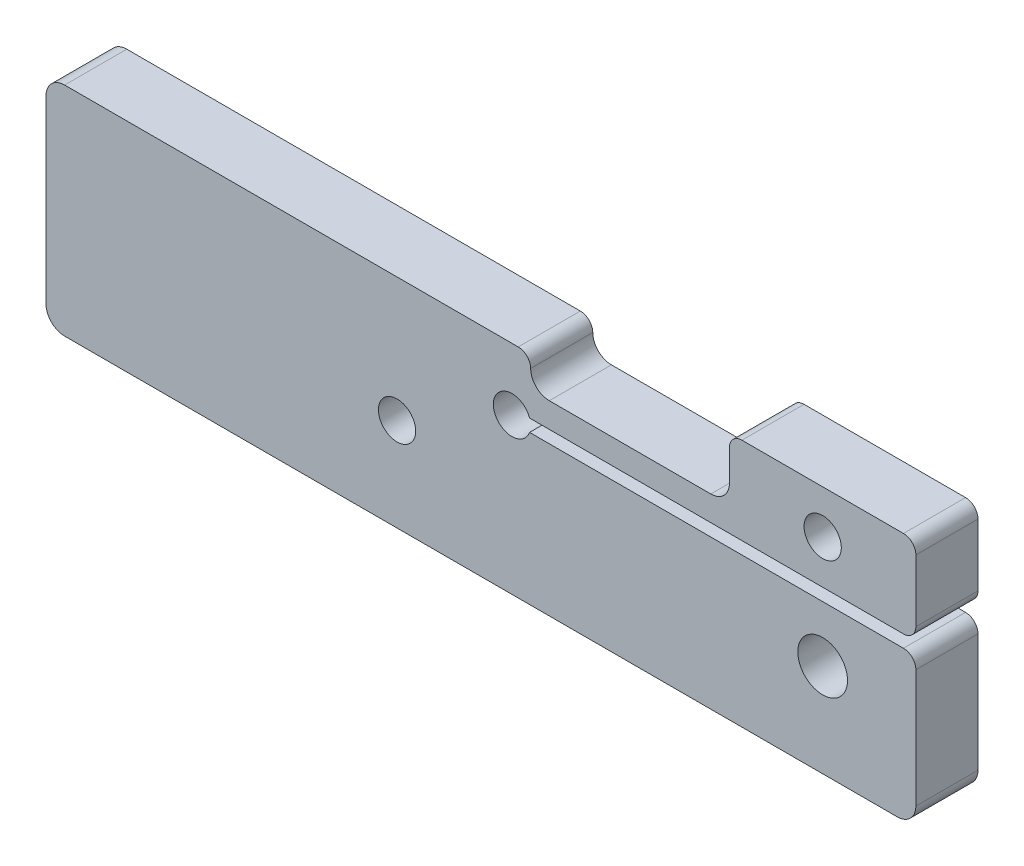
SolidWorks part; units mm, degrees
ref_plane "Front" through (0, 0, 0) normal (0, 0, 1) x (1, 0, 0)
ref_plane "Top" through (0, 0, 0) normal (0, 1, 0) x (1, 0, 0)
ref_plane "Right" through (0, 0, 0) normal (1, 0, 0) x (0, 0, -1)
sketch "Esquisse1" plane through (0, 0, 0) normal (0, 0, 1) x (1, 0, 0)
  line L1 (0, 0) -> (140, 0)
  line L2 (0, 0) -> (0, 35)
  line L3 (0, 35) -> (140, 35)
  line L4 (140, 0) -> (140, 35)
  dimension "D1" = 35
  dimension "D2" = 140
extrude "Boss.-Extru.1" add sketch "Esquisse1" along normal blind 30
sketch "Esquisse2" plane through (0, 0, 30) normal (0, 0, 1) x (1, 0, 0)
  line L0 (0, 0) -> (140, 0) construction
  line L1 (8.5, 0) -> (41.5, 0)
  line L2 (8.5, 0) -> (8.5, 35)
  line L3 (8.5, 35) -> (41.5, 35)
  line L4 (41.5, 0) -> (41.5, 35)
  line L5 (140, 35) -> (0, 35) construction
  line L6 (0, 35) -> (0, 0) construction
  dimension "D1" = 33
  dimension "D2" = 8.5
extrude "Enlèv. mat.-Extru.1" cut sketch "Esquisse2" against normal blind 20
sketch "Esquisse3" plane through (0, 0, 30) normal (0, 0, 1) x (1, 0, 0)
  line L0 (140, 35) -> (41.5, 35) construction
  line L1 (110, 35) -> (140, 35)
  line L2 (110, 35) -> (110, 40)
  line L3 (110, 40) -> (140, 40)
  line L4 (140, 35) -> (140, 40)
  line L5 (140, 0) -> (140, 35) construction
  dimension "D1" = 30
  dimension "D2" = 5
extrude "Boss.-Extru.2" add sketch "Esquisse3" against normal up to vertex (30 mm away)
sketch "Esquisse4" plane through (0, 0, 30) normal (0, 0, 1) x (1, 0, 0)
  line L0 (41.5, 0) -> (140, 0) construction
  line L1 (140, 0) -> (140, 40) construction
  circle A0 centre (75, 25) radius 3
  dimension "D2" = 65
  dimension "D3" = 6
  dimension "D1" = 25
extrude "Enlèv. mat.-Extru.2" cut sketch "Esquisse4" against normal through all both and the other way through all
sketch "Esquisse5" plane through (0, 0, 30) normal (0, 0, 1) x (1, 0, 0)
  line L0 (75, 25) -> (140, 25) construction
  line L1 (140, 0) -> (140, 40) construction
  line L2 (140, 24) -> (140, 26)
  line L3 (140, 26) -> (75, 26)
  line L4 (75, 26) -> (75, 24)
  line L5 (140, 24) -> (75, 24)
  dimension "D1" = 2
extrude "Enlèv. mat.-Extru.3" cut sketch "Esquisse5" against normal through all both and the other way through all
sketch "Esquisse6" plane through (0, 0, 30) normal (0, 0, 1) x (1, 0, 0)
  line L0 (110, 35) -> (41.5, 35) construction
  line L1 (78, 35) -> (110, 35)
  line L2 (78, 35) -> (78, 30)
  line L3 (78, 30) -> (110, 30)
  line L4 (110, 35) -> (110, 30)
  line L5 (140, 26) -> (140, 40) construction
  dimension "D1" = 32
  dimension "D2" = 30
  dimension "D3" = 5
extrude "Enlèv. mat.-Extru.4" cut sketch "Esquisse6" against normal through all both and the other way through all
fillet "Congé1" radius 3 2 edges at (110, 30, 15) (78, 30, 15)
sketch "Esquisse8" plane through (0, 0, 30) normal (0, 0, 1) x (1, 0, 0)
  line L0 (41.5, 0) -> (140, 0) construction
  line L1 (72, 0) -> (140, 0)
  line L3 (106.2756, 24) -> (140, 24)
  line L4 (140, 0) -> (140, 24)
  line L6 (140, 24) -> (77.8284, 24) construction
  line L7 (72, 0) -> (106.2756, 24)
  line L8 (140, 0) -> (140, 24) construction
  line L9 (41.5, 0) -> (140, 0) construction
  dimension "D1" = 35
  dimension "D2" = 68
extrude "Enlèv. mat.-Extru.6" cut sketch "Esquisse8" against normal blind 15
sketch "Esquisse7" plane through (0, 0, 30) normal (0, 0, 1) x (1, 0, 0)
  line L0 (140, 26) -> (140, 40) construction
  line L1 (41.5, 0) -> (72, 0) construction
  circle A0 centre (125, 15) radius 4
  dimension "D1" = 8
  dimension "D2" = 15
  dimension "D3" = 15
extrude "Enlèv. mat.-Extru.5" cut sketch "Esquisse7" against normal through all both and the other way through all
fillet "Congé2" radius 3 4 edges at (140, 0, 7.5) (72, 0, 22.5) (0, 35, 15) (0, 0, 15)
fillet "Congé3" radius 2 12 edges at (106.2756, 24, 22.5) (8.5, 0, 20) (8.5, 35, 20) (41.5, 35, 20) (41.5, 0, 20) (110, 40, 15) (140, 40, 15) (140, 26, 15) (140, 24, 7.5) (78, 34, 0) (78, 35, 15) (78, 34, 30)
sketch "Esquisse10" plane through (0, 0, 30) normal (0, 0, 1) x (1, 0, 0)
  line L0 (140, 33) -> (125, 33) construction
  line L1 (140, 28) -> (140, 38) construction
  line L2 (125, 33) -> (125, 40) construction
  line L3 (138, 40) -> (112, 40) construction
  line L4 (43.5, 0) -> (71.0541, 0) construction
  line L5 (41.5, 2) -> (41.5, 33) construction
  circle A0 centre (56.5, 15) radius 3
  circle A1 centre (125, 33) radius 3
  dimension "D1" = 6
  dimension "D2" = 15
  dimension "D3" = 15
extrude "Enlèv. mat.-Extru.8" cut sketch "Esquisse10" against normal through all both and the other way through all
sketch "Esquisse9" plane through (0, 0, 30) normal (0, 0, 1) x (1, 0, 0)
  line L0 (138, 40) -> (112, 40) construction
  line L1 (0, 0) -> (140, 0)
  line L2 (0, 0) -> (0, 40)
  line L3 (0, 40) -> (140, 40)
  line L4 (140, 0) -> (140, 40)
  line L5 (140, 3) -> (140, 22) construction
extrude "Enlèv. mat.-Extru.7" cut sketch "Esquisse9" against normal up to surface (20 mm away) up to face at (25, 17.5, 10)
